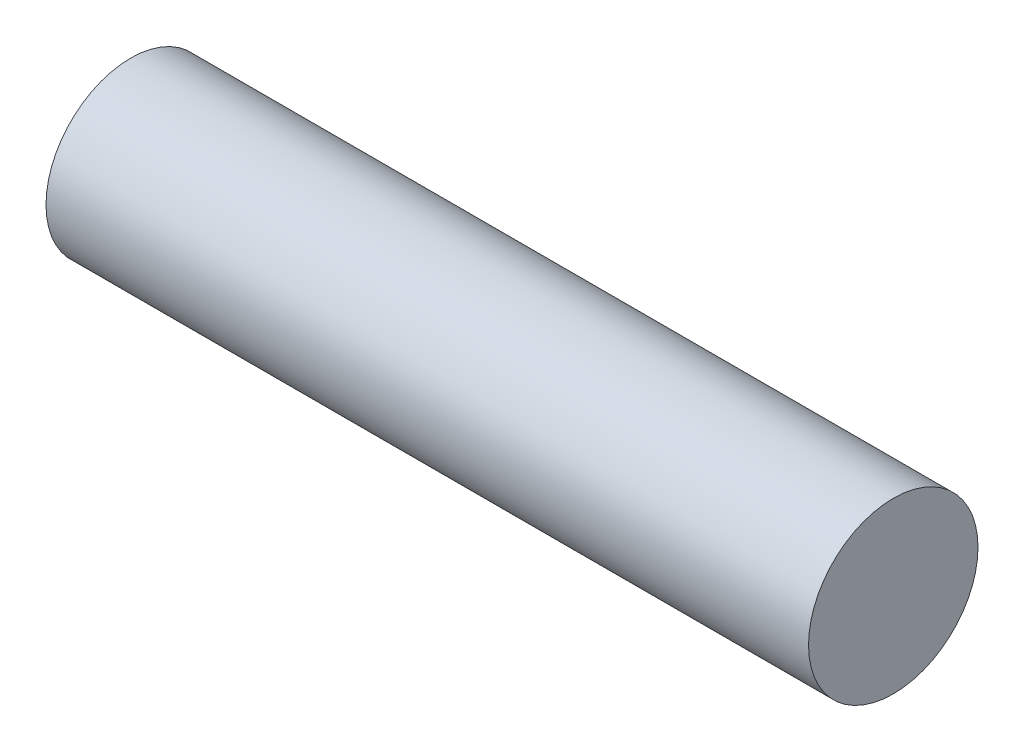
SolidWorks part; units mm, degrees
ref_plane "前视基准面" through (0, 0, 0) normal (0, 0, 1) x (1, 0, 0)
ref_plane "上视基准面" through (0, 0, 0) normal (0, 1, 0) x (1, 0, 0)
ref_plane "右视基准面" through (0, 0, 0) normal (1, 0, 0) x (0, 0, -1)
other "Configuration Table"
sketch "草图1" plane through (0, 0, 0) normal (0, 0, 1) x (1, 0, 0)
  circle A0 centre (0, 0) radius 38
  circle A1 centre (0, 0) radius 33 construction
  circle A2 centre (0, 33) radius 2.5
  circle A3 centre (0, 0) radius 27.5
  dimension "D1" = 76
  dimension "D2" = 66
  dimension "D3" = 5
  dimension "D4" = 55
extrude "凸台-拉伸1" add sketch "草图1" along normal blind 5
sketch "草图2" plane through (0, 0, 0) normal (0, 0, -1) x (-1, 0, 0)
  line L0 (-30.995, 21.9843) -> (-73.1164, -37.4014)
  line L1 (-73.1164, -37.4014) -> (-73.1164, -52.3924)
  line L2 (-73.1164, -52.3924) -> (46.8836, -52.3924)
  line L3 (46.8836, -52.3924) -> (37.521, 6.0146)
  circle A0 centre (0, 0) radius 38 construction
  arc A1 (-30.995, 21.9843) -> (37.521, 6.0146) centre (0, 0) ccw
  dimension "D1" = 120
extrude "凸台-拉伸2" add sketch "草图2" against normal blind 20
fillet "圆角2" radius 2.5 2 edges at (30.995, 21.9843, 12.5) (-37.521, 6.0146, 12.5)
fillet "圆角3" radius 10 1 edges at (-46.8836, -52.3924, 10)
fillet "圆角4" radius 5 2 edges at (73.1164, -52.3924, 10) (73.1164, -37.4014, 10)
mirror "镜向1" about plane through (0, 0, 0) normal (0, 0, 1) of "凸台-拉伸1", "圆角4", "圆角3", "圆角2", "凸台-拉伸2"
sketch "草图3" plane through (0, 0, 20) normal (0, 0, 1) x (1, 0, 0)
  line L1 (-133.1078, 81.3793) -> (133.1078, 81.3793)
  line L2 (-133.1078, 81.3793) -> (-133.1078, -81.3793)
  line L3 (-133.1078, -81.3793) -> (133.1078, -81.3793)
  line L5 (133.1078, 81.3793) -> (133.1078, -81.3793)
  line L6 (-133.1078, 81.3793) -> (133.1078, -81.3793) construction
  line L7 (-133.1078, -81.3793) -> (133.1078, 81.3793) construction
  point P0 (0, 0)
extrude "切除-拉伸1" cut sketch "草图3" against normal blind 20
sketch "草图5" plane through (0, -52.3924, 0) normal (0, -1, 0) x (1, 0, 0)
  line L0 (68.1164, -20) -> (68.1164, 0) construction
  line L1 (-35.153, 0) -> (68.1164, 0)
  line L2 (-35.153, 0) -> (-35.153, -10)
  line L3 (-35.153, -10) -> (68.1164, -10)
  line L4 (68.1164, 0) -> (68.1164, -10)
revolve "旋转1" add sketch "草图5" angle 180 about L3
fillet "圆角5" radius 20 2 edges at (68.1164, -52.3924, -10) (-35.153, -52.3924, -10)
ref_plane "基准面1" through (0, 0, -10) normal (0, 0, 1) x (1, 0, 0)
sketch "草图6" plane through (0, 0, 0) normal (1, 0, 0) x (0, 0, -1)
  line L0 (0, 0) -> (10, 0) construction
  line L1 (10, 0) -> (10, -52.3924) construction
  line L3 (0, 52.3924) -> (20, 52.3924)
  line L4 (0, 52.3924) -> (0, -52.3924)
  line L5 (0, -52.3924) -> (20, -52.3924) construction
  line L6 (20, 52.3924) -> (20, -52.3924)
  line L7 (0, 52.3924) -> (20, -52.3924) construction
  line L8 (0, -52.3924) -> (20, 52.3924) construction
  arc A0 (20, -52.3924) -> (0, -52.3924) centre (10, -52.3924) ccw
extrude "切除-拉伸2" cut sketch "草图6" against normal up to next and the other way up to next
ref_plane "基准面2" through (60, 0, 0) normal (1, 0, 0) x (0, 0, -1)
sketch "草图7" plane through (60, 0, 0) normal (1, 0, 0) x (0, 0, -1)
  circle A0 centre (10, -52.3924) radius 12.317
extrude "切除-拉伸3" cut sketch "草图7" along normal up to next
ref_plane "基准面3" through (-30, 0, 0) normal (1, 0, 0) x (0, 0, -1)
sketch "草图8" plane through (-30, 0, 0) normal (1, 0, 0) x (0, 0, -1)
  circle A0 centre (10, -52.3924) radius 14.1205
extrude "切除-拉伸4" cut sketch "草图8" against normal up to next body kept at (0, -52.3924, -20)
